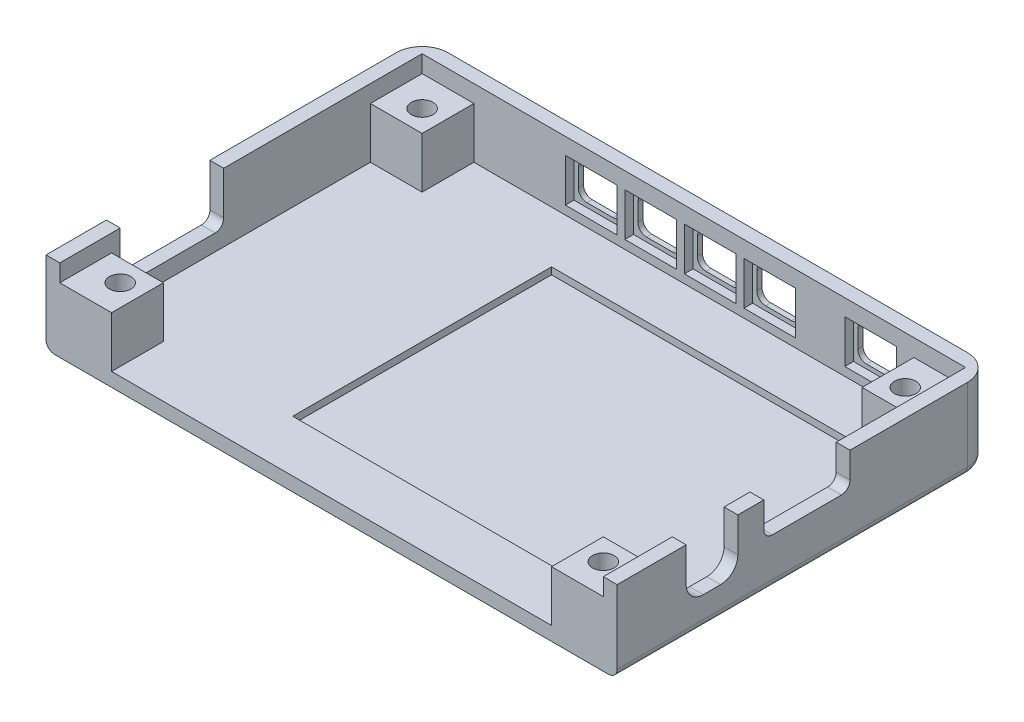
SolidWorks part; units mm, degrees
ref_plane "前视基准面" through (0, 0, 0) normal (0, 0, 1) x (1, 0, 0)
ref_plane "上视基准面" through (0, 0, 0) normal (0, 1, 0) x (1, 0, 0)
ref_plane "右视基准面" through (0, 0, 0) normal (1, 0, 0) x (0, 0, -1)
sketch "草图1" plane through (0, 0, 0) normal (0, 1, 0) x (1, 0, 0)
  line L1 (-31.5, -21) -> (31.5, -21)
  line L2 (-31.5, -21) -> (-31.5, 21)
  line L3 (-31.5, 21) -> (31.5, 21)
  line L4 (31.5, -21) -> (31.5, 21)
  line L5 (-31.5, -21) -> (31.5, 21) construction
  line L6 (-31.5, 21) -> (31.5, -21) construction
  point P0 (0, 0)
  dimension "D1" = 63
  dimension "D2" = 42
extrude "底" add sketch "草图1" against normal blind 1.6
sketch "草图2" plane through (0, 0, 0) normal (0, 1, 0) x (1, 0, 0)
  line L1 (-10.5, -15) -> (31.5, -15)
  line L2 (-10.5, -15) -> (-10.5, 15)
  line L3 (-10.5, 15) -> (31.5, 15)
  line L4 (31.5, -15) -> (31.5, 15)
  line L5 (-10.5, -15) -> (31.5, 15) construction
  line L6 (-10.5, 15) -> (31.5, -15) construction
  line L7 (31.5, 21) -> (-31.5, 21) construction
  line L8 (-31.5, -21) -> (31.5, -21) construction
  line L9 (31.5, -21) -> (31.5, 21) construction
  point P0 (0, 0)
  dimension "D1" = 42
  dimension "D2" = 6
  dimension "D3" = 0
  dimension "D4" = 6
extrude "电池槽" cut sketch "草图2" against normal blind 0.8
sketch "草图4" plane through (0, -1.6, 0) normal (0, -1, 0) x (-1, 0, 0)
  line L0 (-31.5, 21) -> (-31.5, -21)
  line L1 (-31.5, 21) -> (-33.1, 21)
  line L2 (-31.5, -21) -> (-33.1, -21)
  line L3 (-33.1, 21) -> (-33.1, -21)
  line L4 (31.5, 21) -> (31.5, -21)
  line L5 (31.5, 21) -> (33.1, 21)
  line L6 (31.5, -21) -> (33.1, -21)
  line L7 (33.1, 21) -> (33.1, -21)
  dimension "D1" = 1.6
  dimension "D2" = 1.6
extrude "侧边" add sketch "草图4" against normal blind 9.5
sketch "草图5" plane through (0, 0, 0) normal (0, 1, 0) x (1, 0, 0)
  line L0 (-31.5, 21) -> (-31.5, 15)
  line L1 (-31.5, 21) -> (-25.5, 21)
  line L2 (-31.5, 15) -> (-25.5, 15)
  line L3 (-25.5, 21) -> (-25.5, 15)
  line L4 (-31.5, 21) -> (-31.5, -21) construction
  line L5 (25.5, 21) -> (25.5, 15)
  line L6 (25.5, 21) -> (31.5, 21)
  line L7 (25.5, 15) -> (31.5, 15)
  line L8 (31.5, 21) -> (31.5, 15)
  line L9 (-31.5, -15) -> (-31.5, -21)
  line L10 (-31.5, -15) -> (-25.5, -15)
  line L11 (-31.5, -21) -> (-25.5, -21)
  line L12 (-25.5, -15) -> (-25.5, -21)
  line L13 (25.5, -15) -> (25.5, -21)
  line L14 (25.5, -15) -> (31.5, -15)
  line L15 (25.5, -21) -> (31.5, -21)
  line L16 (31.5, -15) -> (31.5, -21)
  dimension "D1" = 6
  dimension "D2" = 6
  dimension "D3" = 6
  dimension "D4" = 6
extrude "螺丝固定" add sketch "草图5" along normal offset from surface (5.9 mm away) 2 up to face at (-32.3, 7.9, 0)
sketch "草图6" plane through (0, 7.9, 0) normal (0, 1, 0) x (1, 0, 0)
  line L0 (-25.5, 15) -> (-25.5, 21) construction
  line L1 (-31.5, 15) -> (-25.5, 15) construction
  circle A0 centre (-28, 17.5) radius 1.25
  circle A1 centre (28, 17.5) radius 1.25
  circle A2 centre (28, -17.5) radius 1.25
  circle A3 centre (-28, -17.5) radius 1.25
  dimension "D1" = 2.5
  dimension "D2" = 2.5
  dimension "D3" = 2.5
  dimension "D4" = 2
  dimension "D5" = 2
extrude "螺丝孔" cut sketch "草图6" against normal up to surface (7.9 mm away) up to face at (-7, 0, 0)
sketch "草图8" plane through (0, 0, 0) normal (0, 1, 0) x (1, 0, 0)
  line L0 (25.5, 21) -> (25.5, 15) construction
  line L1 (-30.5, 20) -> (-25.5, 20)
  line L2 (-30.5, 20) -> (-30.5, 15)
  line L3 (-30.5, 15) -> (-25.5, 15)
  line L4 (-25.5, 20) -> (-25.5, 15)
  line L5 (-30.5, 20) -> (-25.5, 15) construction
  line L6 (-30.5, 15) -> (-25.5, 20) construction
  line L7 (30.5, 20) -> (25.5, 20)
  line L8 (30.5, 20) -> (30.5, 15)
  line L9 (30.5, 15) -> (25.5, 15)
  line L10 (25.5, 20) -> (25.5, 15)
  line L11 (30.5, 20) -> (25.5, 15) construction
  line L12 (30.5, 15) -> (25.5, 20) construction
  line L14 (-30.5, -20) -> (-25.5, -20)
  line L15 (-30.5, -20) -> (-30.5, -15)
  line L16 (-30.5, -15) -> (-25.5, -15)
  line L17 (-25.5, -20) -> (-25.5, -15)
  line L18 (-30.5, -20) -> (-25.5, -15) construction
  line L19 (-30.5, -15) -> (-25.5, -20) construction
  line L20 (30.5, -20) -> (25.5, -20)
  line L21 (30.5, -20) -> (30.5, -15)
  line L22 (30.5, -15) -> (25.5, -15)
  line L23 (25.5, -20) -> (25.5, -15)
  line L24 (30.5, -20) -> (25.5, -15) construction
  line L25 (30.5, -15) -> (25.5, -20) construction
  circle A0 centre (28, 17.5) radius 1.25 construction
  circle A1 centre (28, -17.5) radius 1.25 construction
  circle A2 centre (-28, -17.5) radius 1.25 construction
  circle A3 centre (-28, 17.5) radius 1.25 construction
  circle A4 centre (28, 17.5) radius 1.25 construction
  circle A5 centre (28, -17.5) radius 1.25 construction
  circle A6 centre (-28, -17.5) radius 1.25 construction
  circle A7 centre (-28, 17.5) radius 1.25 construction
sketch "草图9" plane through (0, 0, -21) normal (0, 0, -1) x (-1, 0, 0)
  line L0 (-33.1, 7.9) -> (-33.1, -1.6)
  line L1 (-33.1, 7.9) -> (33.1, 7.9)
  line L2 (-33.1, -1.6) -> (33.1, -1.6)
  line L3 (33.1, 7.9) -> (33.1, -1.6)
extrude "凸台-拉伸4" add sketch "草图9" along normal blind 1.6
sketch "草图10" plane through (0, 0, -21) normal (0, 0, 1) x (1, 0, 0)
  line L1 (17.5, 1) -> (23.5, 1)
  line L2 (17.5, 1) -> (17.5, 6)
  line L3 (17.5, 6) -> (23.5, 6)
  line L4 (23.5, 1) -> (23.5, 6)
  line L5 (17.5, 1) -> (23.5, 6) construction
  line L6 (17.5, 6) -> (23.5, 1) construction
  line L7 (25.5, 0) -> (-25.5, 0) construction
  line L8 (25.5, 5.9) -> (25.5, 0) construction
  line L9 (5.8, 1) -> (11.8, 1)
  line L10 (5.8, 1) -> (5.8, 6)
  line L11 (5.8, 6) -> (11.8, 6)
  line L12 (11.8, 1) -> (11.8, 6)
  line L13 (5.8, 1) -> (11.8, 6) construction
  line L14 (5.8, 6) -> (11.8, 1) construction
  line L15 (-1.1, 1) -> (4.9, 1)
  line L16 (-1.1, 1) -> (-1.1, 6)
  line L17 (-1.1, 6) -> (4.9, 6)
  line L18 (4.9, 1) -> (4.9, 6)
  line L19 (-1.1, 1) -> (4.9, 6) construction
  line L20 (-1.1, 6) -> (4.9, 1) construction
  line L21 (-8, 1) -> (-2, 1)
  line L22 (-8, 1) -> (-8, 6)
  line L23 (-8, 6) -> (-2, 6)
  line L24 (-2, 1) -> (-2, 6)
  line L25 (-8, 1) -> (-2, 6) construction
  line L26 (-8, 6) -> (-2, 1) construction
  line L27 (-14.9, 1) -> (-8.9, 1)
  line L28 (-14.9, 1) -> (-14.9, 6)
  line L29 (-14.9, 6) -> (-8.9, 6)
  line L30 (-8.9, 1) -> (-8.9, 6)
  line L31 (-14.9, 1) -> (-8.9, 6) construction
  line L32 (-14.9, 6) -> (-8.9, 1) construction
  point P0 (20.5, 3.5)
  point P11 (8.8, 3.5)
  point P16 (1.9, 3.5)
  point P21 (-5, 3.5)
  point P26 (-11.9, 3.5)
  dimension "D1" = 6
  dimension "D2" = 5
  dimension "D3" = 5
  dimension "D4" = 3.5
  dimension "D5" = 2
  dimension "D6" = 4
extrude "按键底" cut sketch "草图10" against normal blind 1
sketch "草图12" plane through (0, 0, -22) normal (0, 0, 1) x (1, 0, 0)
  line L0 (17.5, 6) -> (23.5, 1) construction
  line L1 (6.3, 2.5) -> (6.3, 4.5)
  line L2 (19, 1.5) -> (22, 1.5)
  line L3 (18, 2.5) -> (18, 4.5)
  line L4 (23.5, 1) -> (23.5, 6)
  line L5 (23.5, 6) -> (17.5, 6)
  line L6 (17.5, 6) -> (17.5, 1)
  line L7 (17.5, 1) -> (23.5, 1)
  line L8 (23.5, 1) -> (23.5, 6) construction
  line L9 (23.5, 6) -> (17.5, 6) construction
  line L10 (17.5, 6) -> (17.5, 1) construction
  line L11 (17.5, 1) -> (23.5, 1) construction
  line L12 (19, 5.5) -> (22, 5.5)
  line L13 (23, 2.5) -> (23, 4.5)
  line L14 (18, 1.5) -> (23, 5.5) construction
  line L15 (18, 5.5) -> (23, 1.5) construction
  line L16 (7.3, 1.5) -> (10.3, 1.5)
  line L17 (7.3, 5.5) -> (10.3, 5.5)
  line L18 (11.3, 2.5) -> (11.3, 4.5)
  line L19 (-0.6, 2.5) -> (-0.6, 4.5)
  line L20 (0.4, 1.5) -> (3.4, 1.5)
  line L21 (0.4, 5.5) -> (3.4, 5.5)
  line L22 (4.4, 2.5) -> (4.4, 4.5)
  line L23 (-7.5, 2.5) -> (-7.5, 4.5)
  line L24 (-6.5, 1.5) -> (-3.5, 1.5)
  line L25 (-6.5, 5.5) -> (-3.5, 5.5)
  line L26 (-2.5, 2.5) -> (-2.5, 4.5)
  line L27 (-14.4, 2.5) -> (-14.4, 4.5)
  line L28 (-13.4, 1.5) -> (-10.4, 1.5)
  line L29 (-13.4, 5.5) -> (-10.4, 5.5)
  line L30 (-9.4, 2.5) -> (-9.4, 4.5)
  arc A0 (22, 5.5) -> (23, 4.5) centre (22, 4.5) cw
  arc A1 (22, 1.5) -> (23, 2.5) centre (22, 2.5) ccw
  arc A2 (19, 1.5) -> (18, 2.5) centre (19, 2.5) cw
  arc A3 (18, 4.5) -> (19, 5.5) centre (19, 4.5) cw
  arc A4 (6.3, 4.5) -> (7.3, 5.5) centre (7.3, 4.5) cw
  arc A5 (7.3, 1.5) -> (6.3, 2.5) centre (7.3, 2.5) cw
  arc A6 (10.3, 5.5) -> (11.3, 4.5) centre (10.3, 4.5) cw
  arc A7 (10.3, 1.5) -> (11.3, 2.5) centre (10.3, 2.5) ccw
  arc A8 (-0.6, 4.5) -> (0.4, 5.5) centre (0.4, 4.5) cw
  arc A9 (0.4, 1.5) -> (-0.6, 2.5) centre (0.4, 2.5) cw
  arc A10 (3.4, 5.5) -> (4.4, 4.5) centre (3.4, 4.5) cw
  arc A11 (3.4, 1.5) -> (4.4, 2.5) centre (3.4, 2.5) ccw
  arc A12 (-7.5, 4.5) -> (-6.5, 5.5) centre (-6.5, 4.5) cw
  arc A13 (-6.5, 1.5) -> (-7.5, 2.5) centre (-6.5, 2.5) cw
  arc A14 (-3.5, 5.5) -> (-2.5, 4.5) centre (-3.5, 4.5) cw
  arc A15 (-3.5, 1.5) -> (-2.5, 2.5) centre (-3.5, 2.5) ccw
  arc A16 (-14.4, 4.5) -> (-13.4, 5.5) centre (-13.4, 4.5) cw
  arc A17 (-13.4, 1.5) -> (-14.4, 2.5) centre (-13.4, 2.5) cw
  arc A18 (-10.4, 5.5) -> (-9.4, 4.5) centre (-10.4, 4.5) cw
  arc A19 (-10.4, 1.5) -> (-9.4, 2.5) centre (-10.4, 2.5) ccw
  point P2 (20.5, 3.5)
  dimension "D4" = 1
  dimension "D2" = 5
  dimension "D3" = 4
  dimension "D1" = 0
  dimension "D5" = 2
  dimension "D6" = 4
extrude "按键头" cut sketch "草图12" against normal up to next
fillet "圆角4" radius 1 3 edges at (-33.1, -1.6, -0.8) (33.1, -1.6, -0.8) (0, -1.6, -22.6)
fillet "圆角5" radius 3 4 edges at (-32.8071, -1.3071, -22.3071) (32.8071, -1.3071, -22.3071) (33.1, 3.65, -22.6) (-33.1, 3.65, -22.6)
sketch "草图15" plane through (0, 7.9, 0) normal (0, 1, 0) x (1, 0, 0)
  line L16 (33.1, -21) -> (33.1, 19.6)
  line L17 (30.1, 22.6) -> (-30.1, 22.6)
  line L18 (-33.1, 19.6) -> (-33.1, -21)
  line L19 (-33.1, -21) -> (-31.5, -21)
  line L22 (-31.5, -21) -> (-31.5, 21)
  line L25 (-31.5, 21) -> (31.5, 21)
  line L28 (31.5, 21) -> (31.5, -21)
  line L31 (31.5, -21) -> (33.1, -21)
  line L32 (33.1, -21) -> (33.1, 19.6)
  line L33 (30.1, 22.6) -> (-30.1, 22.6)
  line L34 (-33.1, 19.6) -> (-33.1, -21)
  line L35 (-33.1, -21) -> (-31.5, -21)
  line L38 (-31.5, -21) -> (-31.5, 21)
  line L41 (-31.5, 21) -> (31.5, 21)
  line L44 (31.5, 21) -> (31.5, -21)
  line L47 (31.5, -21) -> (33.1, -21)
  arc A2 (33.1, 19.6) -> (30.1, 22.6) centre (30.1, 19.6) ccw
  arc A3 (-30.1, 22.6) -> (-33.1, 19.6) centre (-30.1, 19.6) ccw
  arc A4 (33.1, 19.6) -> (30.1, 22.6) centre (30.1, 19.6) ccw
  arc A5 (-30.1, 22.6) -> (-33.1, 19.6) centre (-30.1, 19.6) ccw
  dimension "D1" = 0
sketch "草图16" plane through (-31.5, 0, 0) normal (1, 0, 0) x (0, 0, -1)
  line L0 (-14, 7.9) -> (-2, 7.9)
  line L1 (-14, 7.9) -> (-14, 2.9)
  line L2 (-2, 7.9) -> (-2, 2.9)
  line L3 (-13, 1.9) -> (-3, 1.9)
  line L4 (-21, 7.9) -> (21, 7.9) construction
  line L5 (-15, 5.9) -> (-15, 0) construction
  arc A0 (-14, 2.9) -> (-13, 1.9) centre (-13, 2.9) ccw
  arc A1 (-2, 2.9) -> (-3, 1.9) centre (-3, 2.9) cw
  point P10 (-14, 1.9)
  point P13 (-2, 1.9)
  dimension "D4" = 1
  dimension "D1" = 12
  dimension "D2" = 6
  dimension "D3" = 1
extrude "tf口" cut sketch "草图16" against normal up to next
sketch "草图17" plane through (31.5, 0, 0) normal (-1, 0, 0) x (0, 0, 1)
  line L0 (7, 7.9) -> (13, 7.9)
  line L1 (7, 7.9) -> (7, 3.9)
  line L2 (13, 7.9) -> (13, 3.9)
  line L3 (9, 1.9) -> (11, 1.9)
  line L4 (-21, 7.9) -> (21, 7.9) construction
  line L5 (15, -0.8) -> (15, 5.9) construction
  line L6 (4, 7.9) -> (-6, 7.9)
  line L7 (4, 7.9) -> (4, 4.9)
  line L8 (-6, 7.9) -> (-6, 4.9)
  line L9 (3, 3.9) -> (-5, 3.9)
  line L11 (21, 7.9) -> (-21, 7.9) construction
  arc A0 (13, 3.9) -> (11, 1.9) centre (11, 3.9) cw
  arc A1 (7, 3.9) -> (9, 1.9) centre (9, 3.9) ccw
  arc A2 (4, 4.9) -> (3, 3.9) centre (3, 4.9) cw
  arc A3 (-6, 4.9) -> (-5, 3.9) centre (-5, 4.9) ccw
  point P10 (13, 1.9)
  point P13 (7, 1.9)
  point P22 (4, 3.9)
  point P25 (-6, 3.9)
  dimension "D4" = 2
  dimension "D8" = 1
  dimension "D1" = 6
  dimension "D2" = 6
  dimension "D3" = 2
  dimension "D5" = 10
  dimension "D6" = 11
  dimension "D7" = 4
extrude "切除-拉伸1" cut sketch "草图17" against normal up to next
